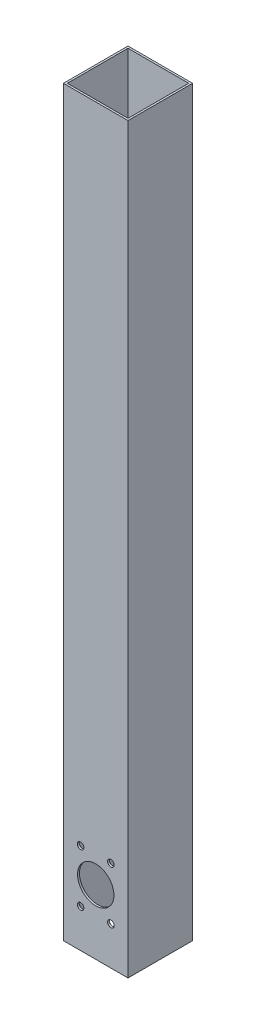
SolidWorks part; units mm, degrees
material "6061 Alloy"
ref_plane "Front Plane" through (0, 0, 0) normal (0, 0, 1) x (1, 0, 0)
ref_plane "Top Plane" through (0, 0, 0) normal (0, 1, 0) x (1, 0, 0)
ref_plane "Right Plane" through (0, 0, 0) normal (1, 0, 0) x (0, 0, -1)
sketch "Sketch1" plane through (0, 0, 0) normal (0, 1, 0) x (1, 0, 0)
  line L1 (25.4, 25.4) -> (-25.4, 25.4)
  line L2 (25.4, 25.4) -> (25.4, -25.4)
  line L3 (25.4, -25.4) -> (-25.4, -25.4)
  line L4 (-25.4, 25.4) -> (-25.4, -25.4)
  line L5 (25.4, 25.4) -> (-25.4, -25.4) construction
  line L6 (25.4, -25.4) -> (-25.4, 25.4) construction
  point P0 (0, 0)
  dimension "D1" = 50.8
extrude "Extrude-Thin1" add sketch "Sketch1" along normal blind 584.2 thin thin type one direction reverse wall 1.524
sketch "Sketch2" plane through (0, 0, 0) normal (0, 0, 1) x (1, 0, 0)
  line L0 (-36.2563, 68.2625) -> (38.5702, 68.2625) construction
  line L1 (-25.4, 0) -> (25.4, 0) construction
  line L2 (-25.4, 50.8) -> (25.4, 50.8) construction
  line L6 (25.4, 584.2) -> (25.4, 0) construction
  line L7 (-25.4, 584.2) -> (-25.4, 0) construction
  line L8 (-11.9126, 30.1668) -> (11.9126, 30.1668) construction
  line L9 (-11.9126, 71.4332) -> (11.9126, 71.4332) construction
  circle A0 centre (0, 50.8) radius 14.3002
  circle A1 centre (0, 50.8) radius 23.8252 construction
  circle A2 centre (-11.9126, 30.1668) radius 2.5908
  circle A3 centre (11.9126, 30.1668) radius 2.5908
  circle A4 centre (11.9126, 71.4332) radius 2.5908
  circle A5 centre (-11.9126, 71.4332) radius 2.5908
  point P11 (0, 50.8)
  dimension "D1" = 28.6004
  dimension "D3" = 17.4625
  dimension "D4" = 47.6504
  dimension "D6" = 5.1816
  dimension "D2" = 50.8
  dimension "D5" = 23.8252
extrude "Cut-Extrude1" cut sketch "Sketch2" along normal through all both and the other way through all
